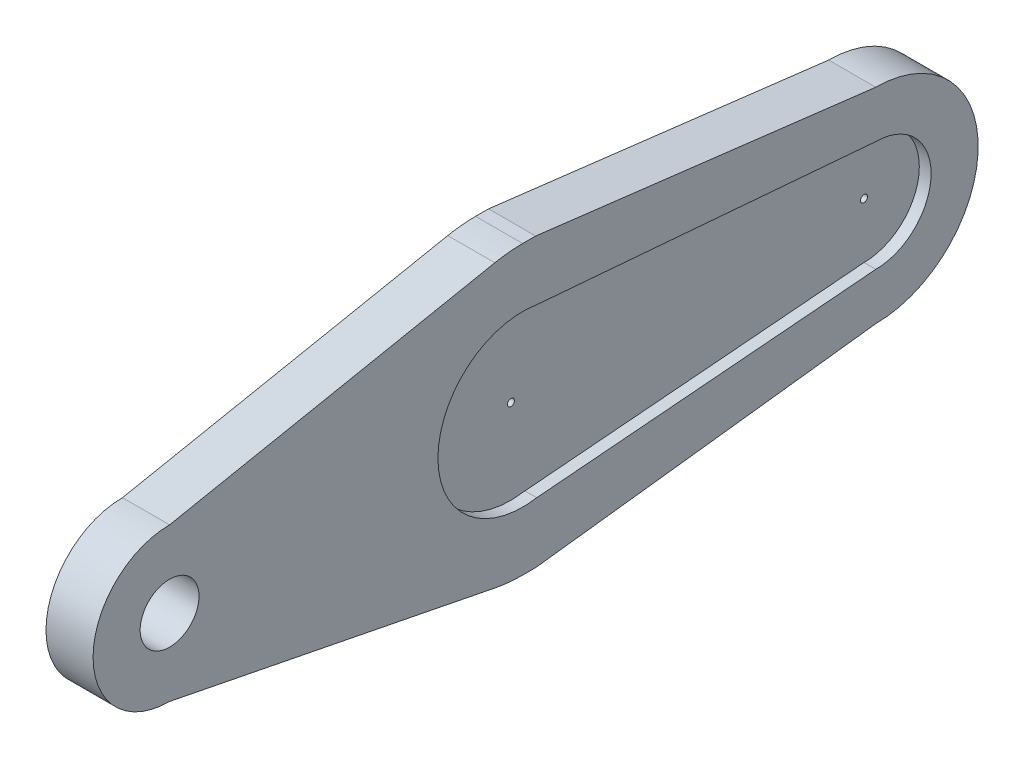
SolidWorks part; units mm, degrees
material "PLA"
ref_plane "Front Plane" through (0, 0, 0) normal (1, 0, 0) x (0, 1, 0)
ref_plane "Top Plane" through (0, 0, 0) normal (0, 0, 1) x (0, 1, 0)
ref_plane "Right Plane" through (0, 0, 0) normal (0, 1, 0) x (-1, 0, 0)
sketch "Sketch2" plane through (0, 0, 0) normal (1, 0, 0) x (0, 1, 0)
  line L0 (0, -13.9832) -> (0, -33.5576) construction
  line L1 (-6.1, -18.8) -> (6.1, -18.8)
  line L2 (-6.1, -18.8) -> (-6.1, 18.8)
  line L3 (-6.1, 18.8) -> (6.1, 18.8)
  line L4 (6.1, -18.8) -> (6.1, 18.8)
  line L5 (-6.1, -18.8) -> (6.1, 18.8) construction
  line L6 (-6.1, 18.8) -> (6.1, -18.8) construction
  line L7 (2.35, -14.45) -> (3.6, 0.55)
  line L8 (-3.6, 0.55) -> (-2.35, -14.45)
  line L9 (-6.1, 0) -> (-4.35, -14.45)
  line L10 (4.35, -14.45) -> (6.1, 0)
  line L11 (-3.25, 15.55) -> (-5.984, 1.7341)
  line L12 (5.984, 1.7341) -> (3.25, 15.55)
  arc A1 (3.5503, -0.0459) -> (-3.5503, -0.0459) centre (0, 0.55) ccw
  arc A2 (-2.35, -14.45) -> (2.35, -14.45) centre (0, -14.45) ccw
  circle A3 centre (0, 15.55) radius 1.25
  arc A4 (3.25, 15.55) -> (-3.25, 15.55) centre (0, 15.55) ccw
  arc A5 (-4.35, -14.45) -> (4.35, -14.45) centre (0, -14.45) ccw
  arc A6 (-5.984, 1.7341) -> (-6.1, 0.55) centre (0, 0.55) ccw
  arc A7 (6.1, 0.55) -> (5.984, 1.7341) centre (0, 0.55) ccw
  point P0 (0, 0)
  dimension "D1" = 7.2
  dimension "D2" = 4.7
  dimension "D4" = 2.5
  dimension "D5" = 2
  dimension "D8" = 2
  dimension "D3" = 15
  dimension "D6" = 15
  dimension "D7" = 2.5
extrude "Boss-Extrude1" add sketch "Sketch2" along normal blind 2 contours L4 A7 L12 A4 L11 A6 L2 L9 A5 L10 A3 A2 L8 A1 L7 region at (0, -2.7964, -17.2464)
extrude "Boss-Extrude2" add sketch "Sketch2<3>" along normal blind 1.5 contours L8 A2 L7 A1 region at (0, 0, -5.6231)
sketch "Sketch2<3>" plane through (0, 0, 0) normal (1, 0, 0) x (0, 1, 0) same geometry as "Sketch2"
sketch "Sketch3" plane through (1.5, 0, 0) normal (1, 0, 0) x (0, 1, 0)
  circle A0 centre (0, 0.55) radius 0.15
  arc A1 (3.6, 0.55) -> (-3.6, 0.55) centre (0, 0.55) ccw construction
  circle A2 centre (0, -14.45) radius 0.15
  arc A3 (-2.35, -14.45) -> (2.35, -14.45) centre (0, -14.45) ccw construction
  dimension "D1" = 0.3
extrude "Cut-Extrude1" cut sketch "Sketch3" against normal through all
